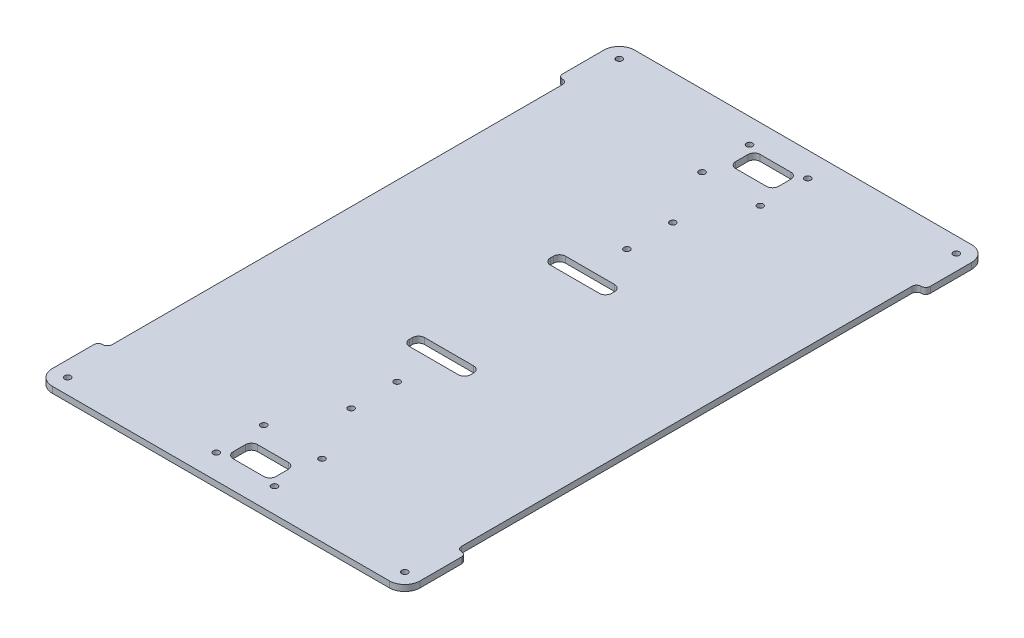
SolidWorks part; units mm, degrees
ref_plane "Plano frontal" through (0, 0, 0) normal (0, 0, 1) x (1, 0, 0)
ref_plane "Plano superior" through (0, 0, 0) normal (0, 1, 0) x (1, 0, 0)
ref_plane "Plano direito" through (0, 0, 0) normal (1, 0, 0) x (0, 0, -1)
sketch "Esboço1" plane through (0, 0, 0) normal (0, 1, 0) x (1, 0, 0)
  line L1 (-60, -95) -> (60, -95)
  line L2 (-60, -95) -> (-60, 95)
  line L3 (-60, 95) -> (60, 95)
  line L4 (60, -95) -> (60, 95)
  line L5 (-60, -95) -> (60, 95) construction
  line L6 (-60, 95) -> (60, -95) construction
  point P0 (0, 0)
  dimension "D1" = 120
  dimension "D2" = 190
extrude "Ressalto-extrusão1" add sketch "Esboço1" along normal blind 2
sketch "Esboço2" plane through (0, 2, 0) normal (0, 1, 0) x (1, 0, 0)
  line L0 (0, 95) -> (0, -95) construction
  line L1 (60, 95) -> (-60, 95) construction
  line L2 (-60, -95) -> (60, -95) construction
  line L4 (-60, -45) -> (60, -45) construction
  line L5 (-60, 95) -> (-60, -95) construction
  line L6 (60, -95) -> (60, 95) construction
  line L7 (-60, 0) -> (60, 0) construction
  circle A0 centre (0, -37.5) radius 1
  circle A1 centre (0, -52.5) radius 1
  circle A2 centre (0, 52.5) radius 1
  circle A3 centre (0, 37.5) radius 1
  dimension "D1" = 2
  dimension "D2" = 15
  dimension "D3" = 45
extrude "Corte-extrusão1" cut sketch "Esboço2" against normal blind 10
sketch "Esboço3" plane through (0, 2, 0) normal (0, 1, 0) x (1, 0, 0)
  line L0 (60, 95) -> (-60, 95) construction
  line L1 (-60, 95) -> (-60, -95) construction
  line L2 (0, 95) -> (0, -95) construction
  line L3 (-60, -95) -> (60, -95) construction
  line L4 (-60, 0) -> (60, 0) construction
  line L5 (60, -95) -> (60, 95) construction
  circle A0 centre (-55, 90) radius 1
  circle A1 centre (55, 90) radius 1
  circle A2 centre (55, -90) radius 1
  circle A3 centre (-55, -90) radius 1
  dimension "D1" = 2
  dimension "D2" = 110
  dimension "D3" = 180
extrude "Corte-extrusão2" cut sketch "Esboço3" against normal through all
fillet "Filete1" radius 5 4 edges at (-60, 1, -95) (60, 1, -95) (60, 1, 95) (-60, 1, 95)
sketch "Esboço4" plane through (0, 2, 0) normal (0, 1, 0) x (1, 0, 0)
  line L0 (60, -90) -> (60, 90) construction
  line L1 (60, 75) -> (57, 75)
  line L2 (60, 75) -> (60, -75)
  line L3 (60, -75) -> (57, -75)
  line L4 (57, 75) -> (57, -75)
  line L5 (-55, -95) -> (55, -95) construction
  line L6 (55, 95) -> (-55, 95) construction
  dimension "D1" = 3
  dimension "D2" = 20
  dimension "D3" = 20
extrude "Corte-extrusão3" cut sketch "Esboço4" against normal through all
mirror "Espelhar1" about plane through (0, 0, 0) normal (1, 0, 0) of "Corte-extrusão3"
fillet "Filete2" radius 1.5 8 edges at (57, 1, 75) (60, 1, 75) (57, 1, -75) (60, 1, -75) (-57, 1, 75) (-60, 1, 75) (-57, 1, -75) (-60, 1, -75)
sketch "Esboço5" plane through (0, 0, 0) normal (0, -1, 0) x (1, 0, 0)
  line L0 (0, 95) -> (0, -95) construction
  line L1 (-8, 25.5) -> (8, 25.5)
  line L2 (-10, 23.5) -> (-10, 22.5)
  line L3 (-8, 20.5) -> (8, 20.5)
  line L4 (10, 23.5) -> (10, 22.5)
  line L5 (-10, 25.5) -> (10, 20.5) construction
  line L6 (-10, 20.5) -> (10, 25.5) construction
  line L7 (-55, 95) -> (55, 95) construction
  line L8 (55, -95) -> (-55, -95) construction
  line L9 (-57, 0) -> (57, 0) construction
  line L10 (-57, -73.5) -> (-57, 73.5) construction
  line L11 (57, -73.5) -> (57, 73.5) construction
  line L12 (-10, -20.5) -> (10, -25.5) construction
  line L13 (-10, -25.5) -> (10, -20.5) construction
  line L14 (10, -23.5) -> (10, -22.5)
  line L15 (-8, -20.5) -> (8, -20.5)
  line L16 (-10, -23.5) -> (-10, -22.5)
  line L17 (-8, -25.5) -> (8, -25.5)
  arc A0 (8, 25.5) -> (10, 23.5) centre (8, 23.5) cw
  arc A1 (10, 22.5) -> (8, 20.5) centre (8, 22.5) cw
  arc A2 (-10, 22.5) -> (-8, 20.5) centre (-8, 22.5) ccw
  arc A3 (-10, 23.5) -> (-8, 25.5) centre (-8, 23.5) cw
  arc A4 (-10, -23.5) -> (-8, -25.5) centre (-8, -23.5) ccw
  arc A5 (-10, -22.5) -> (-8, -20.5) centre (-8, -22.5) cw
  arc A6 (10, -22.5) -> (8, -20.5) centre (8, -22.5) ccw
  arc A7 (8, -25.5) -> (10, -23.5) centre (8, -23.5) ccw
  point P0 (0, 23)
  point P46 (0, -23)
  dimension "D3" = 2
  dimension "D4" = 46
  dimension "D1" = 5
  dimension "D2" = 20
extrude "Corte-extrusão4" cut sketch "Esboço5" against normal blind 10
sketch "Esboço6" plane through (0, 0, 0) normal (0, -1, 0) x (1, 0, 0)
  line L0 (0, 95) -> (0, 0) construction
  line L1 (-55, 95) -> (55, 95) construction
  line L2 (9.5, 95) -> (9.5, 71.5) construction
  line L3 (-5, 86) -> (5, 86)
  line L4 (-7, 84) -> (-7, 80)
  line L5 (-5, 78) -> (5, 78)
  line L6 (7, 84) -> (7, 80)
  line L7 (-7, 86) -> (7, 78) construction
  line L8 (-7, 78) -> (7, 86) construction
  arc A0 (5, 86) -> (7, 84) centre (5, 84) cw
  arc A1 (5, 78) -> (7, 80) centre (5, 80) ccw
  arc A2 (-7, 80) -> (-5, 78) centre (-5, 80) ccw
  arc A3 (-7, 84) -> (-5, 86) centre (-5, 84) cw
  circle A4 centre (9.5, 87) radius 1
  circle A5 centre (9.5, 71.5) radius 1
  circle A6 centre (-9.5, 87) radius 1
  circle A7 centre (-9.5, 71.5) radius 1
  point P5 (0, 82)
  dimension "D4" = 2
  dimension "D5" = 2
  dimension "D6" = 19
  dimension "D7" = 15.5
  dimension "D8" = 8
  dimension "D1" = 9
  dimension "D2" = 8
  dimension "D3" = 14
extrude "Corte-extrusão5" cut sketch "Esboço6" against normal blind 10
mirror "Espelhar2" about plane through (0, 0, 0) normal (0, 0, 1) of "Corte-extrusão5"
